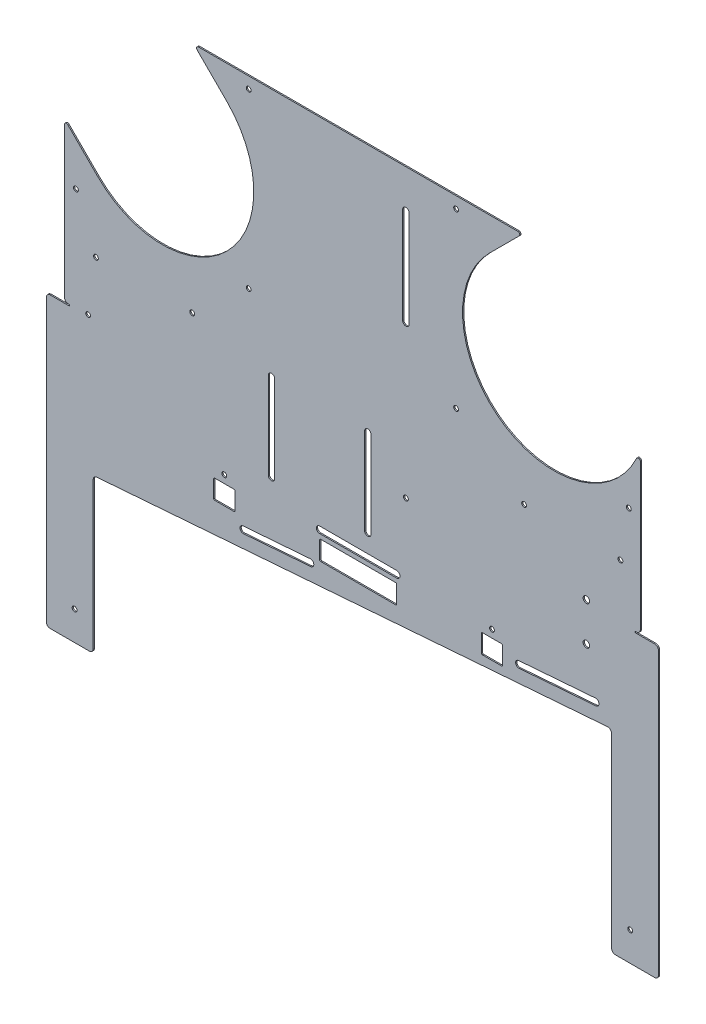
SolidWorks part; units mm, degrees
material "Plain Carbon Steel"
ref_plane "Front Plane" through (0, 0, 0) normal (0, 0, 1) x (1, 0, 0)
ref_plane "Top Plane" through (0, 0, 0) normal (0, 1, 0) x (1, 0, 0)
ref_plane "Right Plane" through (0, 0, 0) normal (1, 0, 0) x (0, 0, -1)
sketch "Model" plane through (0, 0, 0) normal (0, 0, 1) x (1, 0, 0)
  line L0 (179, 130) -> (179, 180)
  line L1 (175.6, 180) -> (175.6, 130)
  line L2 (155.85, 70.5824) -> (155.85, 25.5824)
  line L3 (159.15, 25.5824) -> (159.15, 70.5824)
  line L4 (109.15, 25.5824) -> (109.15, 70.5824)
  line L5 (105.85, 70.5824) -> (105.85, 25.5824)
  line L6 (172.5, 16.0516) -> (132.5, 16.0516)
  line L7 (132.5, 12.6516) -> (172.5, 12.6516)
  line L8 (275.6995, 10.2875) -> (235.8173, 7.2196)
  line L9 (275.9603, 6.8975) -> (236.0781, 3.8296)
  line L10 (77.5, 0.8516) -> (77.5, 9.8516)
  line L11 (78, 10.3516) -> (88, 10.3516)
  line L12 (88.5, 9.8516) -> (88.5, 0.8516)
  line L13 (78, 0.3516) -> (88, 0.3516)
  line L14 (216.5, 9.8516) -> (216.5, 0.8516)
  line L15 (217, 10.3516) -> (227, 10.3516)
  line L16 (227.5, 0.8516) -> (227.5, 9.8516)
  line L17 (217, 0.3516) -> (227, 0.3516)
  line L18 (132.5, 9.8516) -> (132.5, 0.8516)
  line L19 (133, 10.3516) -> (172, 10.3516)
  line L20 (172.5, 9.8516) -> (172.5, 0.8516)
  line L21 (133, 0.3516) -> (172, 0.3516)
  line L22 (127.8753, -4.4937) -> (92.9784, -7.178)
  line L23 (127.6145, -1.1037) -> (92.7176, -3.788)
  line L24 (0, 130.4106) -> (0, 52.635)
  line L25 (2.6416, 50.635) -> (2, 50.635)
  line L26 (2.6416, 50) -> (2.6416, 50.635)
  line L27 (-7.4113, 50) -> (2.6416, 50)
  line L28 (-9.4113, -98) -> (-9.4113, 48)
  line L29 (-7.4113, -100) -> (12.9289, -100)
  line L30 (14.9289, -98) -> (14.9289, -21.8521)
  line L31 (16.7755, -19.858) -> (281.9178, 0.5376)
  line L32 (284.0711, -1.4565) -> (284.0711, -98)
  line L33 (286.0711, -100) -> (306.4113, -100)
  line L34 (308.4113, 48) -> (308.4113, -98)
  line L35 (296.3584, 50) -> (306.4113, 50)
  line L36 (296.3584, 50.635) -> (296.3584, 50)
  line L37 (297, 50.635) -> (296.3584, 50.635)
  line L38 (299, 52.635) -> (299, 128.3719)
  line L39 (220.6124, 182.7876) -> (236.1177, 198.2929)
  line L40 (235.4106, 200) -> (69.5894, 200)
  line L41 (84.3876, 182.7876) -> (68.8823, 198.2929)
  line L42 (1.7071, 131.1177) -> (17.2124, 115.6124)
  arc A0 (179, 180) -> (175.6, 180) centre (177.3, 180) ccw
  arc A1 (175.6, 130) -> (179, 130) centre (177.3, 130) ccw
  circle A2 centre (177.3, 51) radius 1.25
  circle A3 centre (12.3, 51) radius 1.25
  circle A4 centre (271, 32.2) radius 1.7
  circle A5 centre (271, 52.2) radius 1.7
  circle A6 centre (5.25, -84.9) radius 1.25
  circle A7 centre (293.75, -84.9) radius 1.25
  arc A8 (155.85, 25.5824) -> (159.15, 25.5824) centre (157.5, 25.5824) ccw
  arc A9 (159.15, 70.5824) -> (155.85, 70.5824) centre (157.5, 70.5824) ccw
  arc A10 (109.15, 70.5824) -> (105.85, 70.5824) centre (107.5, 70.5824) ccw
  arc A11 (105.85, 25.5824) -> (109.15, 25.5824) centre (107.5, 25.5824) ccw
  arc A12 (132.5, 16.0516) -> (132.5, 12.6516) centre (132.5, 14.3516) ccw
  arc A13 (172.5, 12.6516) -> (172.5, 16.0516) centre (172.5, 14.3516) ccw
  circle A14 centre (83, 14.3516) radius 1.25
  circle A15 centre (222, 14.3516) radius 1.25
  arc A16 (235.8173, 7.2196) -> (236.0781, 3.8296) centre (235.9477, 5.5246) ccw
  arc A17 (275.9603, 6.8975) -> (275.6995, 10.2875) centre (275.8299, 8.5925) ccw
  arc A18 (78, 10.3516) -> (77.5, 9.8516) centre (78, 9.8516) ccw
  arc A19 (88.5, 9.8516) -> (88, 10.3516) centre (88, 9.8516) ccw
  arc A20 (88, 0.3516) -> (88.5, 0.8516) centre (88, 0.8516) ccw
  arc A21 (77.5, 0.8516) -> (78, 0.3516) centre (78, 0.8516) ccw
  arc A22 (217, 10.3516) -> (216.5, 9.8516) centre (217, 9.8516) ccw
  arc A23 (227.5, 9.8516) -> (227, 10.3516) centre (227, 9.8516) ccw
  arc A24 (227, 0.3516) -> (227.5, 0.8516) centre (227, 0.8516) ccw
  arc A25 (216.5, 0.8516) -> (217, 0.3516) centre (217, 0.8516) ccw
  circle A26 centre (238.6616, 78.8319) radius 1.25
  circle A27 centre (16.3384, 78.8315) radius 1.25
  circle A28 centre (203.3563, 104.3563) radius 1.25
  circle A29 centre (95.6437, 104.3563) radius 1.25
  circle A30 centre (95.6437, 194.0437) radius 1.25
  circle A31 centre (5.9563, 104.3563) radius 1.25
  circle A32 centre (203.3563, 194.0437) radius 1.25
  circle A33 centre (293.0437, 104.3563) radius 1.25
  circle A34 centre (66.3384, 78.8315) radius 1.25
  circle A35 centre (288.6616, 78.8319) radius 1.25
  arc A36 (133, 10.3516) -> (132.5, 9.8516) centre (133, 9.8516) ccw
  arc A37 (172.5, 9.8516) -> (172, 10.3516) centre (172, 9.8516) ccw
  arc A38 (172, 0.3516) -> (172.5, 0.8516) centre (172, 0.8516) ccw
  arc A39 (132.5, 0.8516) -> (133, 0.3516) centre (133, 0.8516) ccw
  arc A40 (127.8753, -4.4937) -> (127.6145, -1.1037) centre (127.7449, -2.7987) ccw
  arc A41 (92.7176, -3.788) -> (92.9784, -7.178) centre (92.848, -5.483) ccw
  arc A42 (0, 52.635) -> (2, 50.635) centre (2, 52.635) ccw
  arc A43 (-7.4113, 50) -> (-9.4113, 48) centre (-7.4113, 48) ccw
  arc A44 (-9.4113, -98) -> (-7.4113, -100) centre (-7.4113, -98) ccw
  arc A45 (12.9289, -100) -> (14.9289, -98) centre (12.9289, -98) ccw
  arc A46 (16.7755, -19.858) -> (14.9289, -21.8521) centre (16.9289, -21.8521) ccw
  arc A47 (284.0711, -1.4565) -> (281.9178, 0.5376) centre (282.0711, -1.4565) ccw
  arc A48 (284.0711, -98) -> (286.0711, -100) centre (286.0711, -98) ccw
  arc A49 (306.4113, -100) -> (308.4113, -98) centre (306.4113, -98) ccw
  arc A50 (308.4113, 48) -> (306.4113, 50) centre (306.4113, 48) ccw
  arc A51 (297, 50.635) -> (299, 52.635) centre (297, 52.635) ccw
  arc A52 (299, 128.3719) -> (297.0969, 128.8013) centre (298, 128.3719) ccw
  arc A53 (220.6124, 182.7876) -> (297.0969, 128.8013) centre (254.2, 149.2) ccw
  arc A54 (236.1177, 198.2929) -> (235.4106, 200) centre (235.4106, 199) ccw
  arc A55 (69.5894, 200) -> (68.8823, 198.2929) centre (69.5894, 199) ccw
  arc A56 (17.2124, 115.6124) -> (84.3876, 182.7876) centre (50.8, 149.2) ccw
  arc A57 (1.7071, 131.1177) -> (0, 130.4106) centre (1, 130.4106) ccw
sheet metal parameters "Sheet-Metal1" thickness 0.635 parameters "D1"=0.7366
base flange "Base-Flange1" sketch "Model" thickness 0.635 reverse thickness direction no parameters "D1"=0.7366
flat pattern "Flat-Pattern1" [suppressed]
sketch "Bend-Lines1" plane through (0, 0, 0) normal (0, 1, 0) x (1, 0, 0)
sketch3d "Bounding-Box1" [suppressed]
  line L0 (11.4111, 147.3651, 0) -> (-306.4114, 147.365, 0) construction
  line L1 (11.4113, -152.6348, 0) -> (-306.4112, -152.635, 0) construction
  line L2 (11.4111, 147.3651, 0) -> (11.4113, -152.6348, 0) construction
  line L3 (-306.4114, 147.365, 0) -> (-306.4112, -152.635, 0) construction
